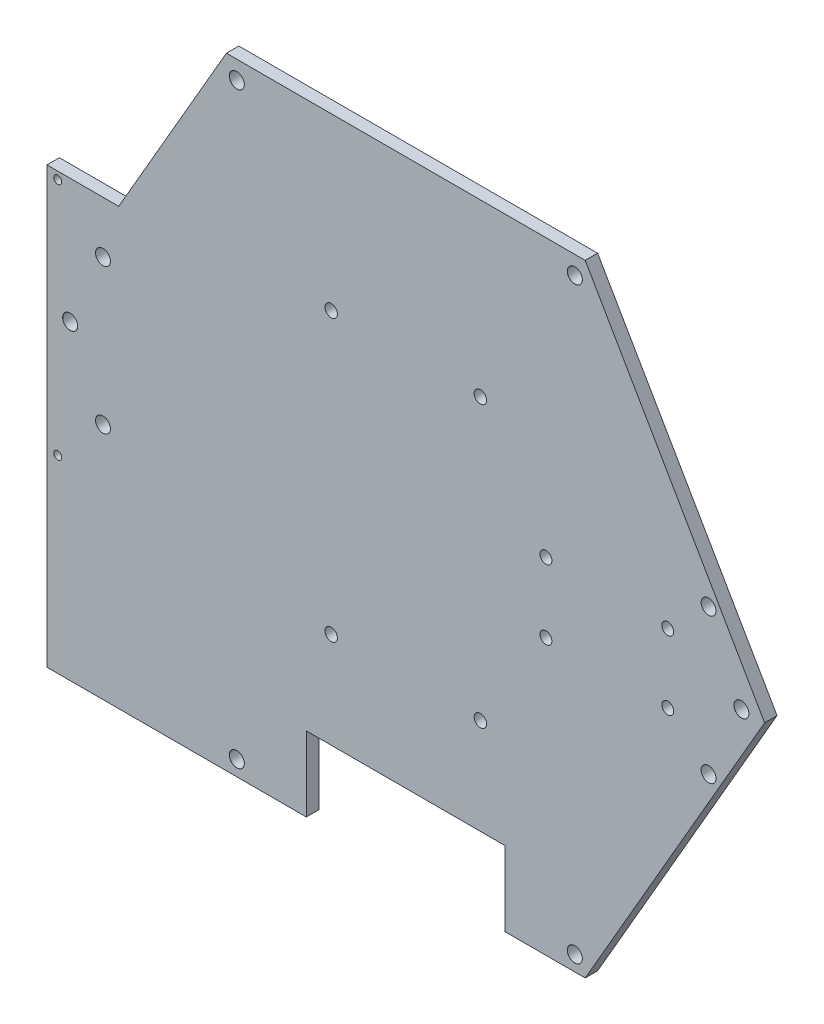
SolidWorks part; units mm, degrees
ref_plane "前视基准面" through (0, 0, 0) normal (0, 0, 1) x (1, 0, 0)
ref_plane "上视基准面" through (0, 0, 0) normal (0, 1, 0) x (1, 0, 0)
ref_plane "右视基准面" through (0, 0, 0) normal (1, 0, 0) x (0, 0, -1)
other "Configuration Table"
sketch "草图8" plane through (0, 0, 0) normal (0, 0, 1) x (1, 0, 0)
  line L0 (0, -95) -> (0, 125) construction
  line L1 (144.3376, 0) -> (72.1688, 125)
  line L2 (72.1688, 125) -> (-72.1688, 125)
  line L3 (-72.1688, 125) -> (-144.3376, 0)
  line L4 (-144.3376, 0) -> (-72.1688, -125)
  line L5 (-72.1688, -125) -> (-40, -125)
  line L6 (72.1688, -125) -> (144.3376, 0)
  line L7 (0, 125) -> (0, -95) construction
  line L8 (-40, -125) -> (-40, -95)
  line L9 (-40, -95) -> (40, -95)
  line L10 (40, -125) -> (40, -95)
  line L11 (40, -125) -> (72.1688, -125)
  arc A0 (40, -118.4272) -> (-40, -118.4272) centre (0, 0) ccw construction
  point P15 (0, -95)
  dimension "D1" = 250
  dimension "D2" = 40
  dimension "D3" = 30
extrude "凸台-拉伸3" add sketch "草图8" along normal blind 5
sketch "草图19" plane through (0, 0, 5) normal (0, 0, 1) x (1, 0, 0)
  point P0 (-135.0031, 0)
  point P2 (-67.9807, -118.8668)
  point P4 (-67.9807, 117.662)
hole_wizard "Ø6.0 (6) 直径孔1" positions "草图19" profile "草图18" hole size "Ø6.0" standard "GB" end condition through all
sketch "草图18" plane through (-135.0031, 0, 5) normal (1, 0, 0) x (0, -1, 0)
  line L0 (0, 0) -> (0, 5)
  line L1 (0, 5) -> (3, 5)
  line L2 (3, 5) -> (3, 0.025)
  line L3 (3, 0.025) -> (3.025, 0)
  line L5 (3.025, 0) -> (0, 0)
  line L6 (-3, 0.025) -> (-3.025, 0) construction
  line L11 (0, -6.35) -> (0, 107.95) construction
  dimension "通孔孔直径" = 6
  dimension "通孔孔深度" = 5
  dimension "近端锥形沉头孔直径" = 6.05
  dimension "近端锥形沉头孔角度" = 90
mirror "镜向2" about plane through (0, 0, 0) normal (1, 0, 0) of "Ø6.0 (6) 直径孔1"
sketch "草图20" plane through (0, 0, 5) normal (0, 0, 1) x (1, 0, 0)
  circle A0 centre (56.3709, 13.653) radius 2.4
  circle A1 centre (105.3709, 13.3246) radius 2.4
  circle A2 centre (56.3709, -14.347) radius 2.4
  circle A3 centre (105.3709, -14.347) radius 2.4
  dimension "D1" = 4.8
  dimension "D2" = 28
  dimension "D3" = 49
extrude "切除-拉伸2" cut sketch "草图20" against normal through all
sketch "草图32" plane through (0, 0, 0) normal (0, 0, 1) x (1, 0, 0)
  line L0 (0, 125) -> (0, -96.202) construction
  line L1 (72.1688, 125) -> (-72.1688, 125) construction
sketch "草图33" plane through (0, 0, 5) normal (0, 0, 1) x (1, 0, 0)
  line L0 (0, 125) -> (0, -95) construction
  line L1 (-40, -95) -> (40, -95) construction
  line L2 (-144.3376, 0) -> (144.3376, 0) construction
  circle A0 centre (-121.7978, -29.1812) radius 3
  circle A1 centre (121.7978, -29.1812) radius 3
  circle A2 centre (121.7978, 29.1812) radius 3
  circle A3 centre (-121.7978, 29.1812) radius 3
extrude "切除-拉伸3" cut sketch "草图33" against normal through all
sketch "草图34" plane through (0, 0, 5) normal (0, 0, 1) x (1, 0, 0)
  line L0 (0, 125) -> (0, -96.202) construction
  line L1 (-144.3376, 0) -> (144.3376, 0) construction
  circle A0 centre (-30, -56.3924) radius 2.5
  circle A1 centre (30, -56.3924) radius 2.5
  circle A2 centre (30, 56.3924) radius 2.5
  circle A3 centre (-30, 56.3924) radius 2.5
extrude "切除-拉伸4" cut sketch "草图34" against normal through all
sketch "草图35" plane through (0, 0, 0) normal (0, 0, 1) x (1, 0, 0)
  line L0 (-115.4701, 50) -> (-144.3376, 50)
  line L1 (-72.1688, 125) -> (-144.3376, 0) construction
  line L2 (-144.3376, 50) -> (-144.3376, -125)
  line L3 (-144.3376, -125) -> (-72.1688, -125)
  line L4 (-72.1688, -125) -> (-144.3376, 0)
  line L5 (-144.3376, 0) -> (-115.4701, 50)
  circle A0 centre (-140, 47) radius 1.6
  circle A1 centre (-140, -49) radius 1.6
  dimension "D1" = 50
  dimension "D2" = 0
extrude "凸台-拉伸5" add sketch "草图35" along normal blind 5 contours L2 L5 L0 A0 | L3 L4 L2 A1 region at (-134.6555, 33.1793, 0) region at (-120.2461, -83.3947, 0)
